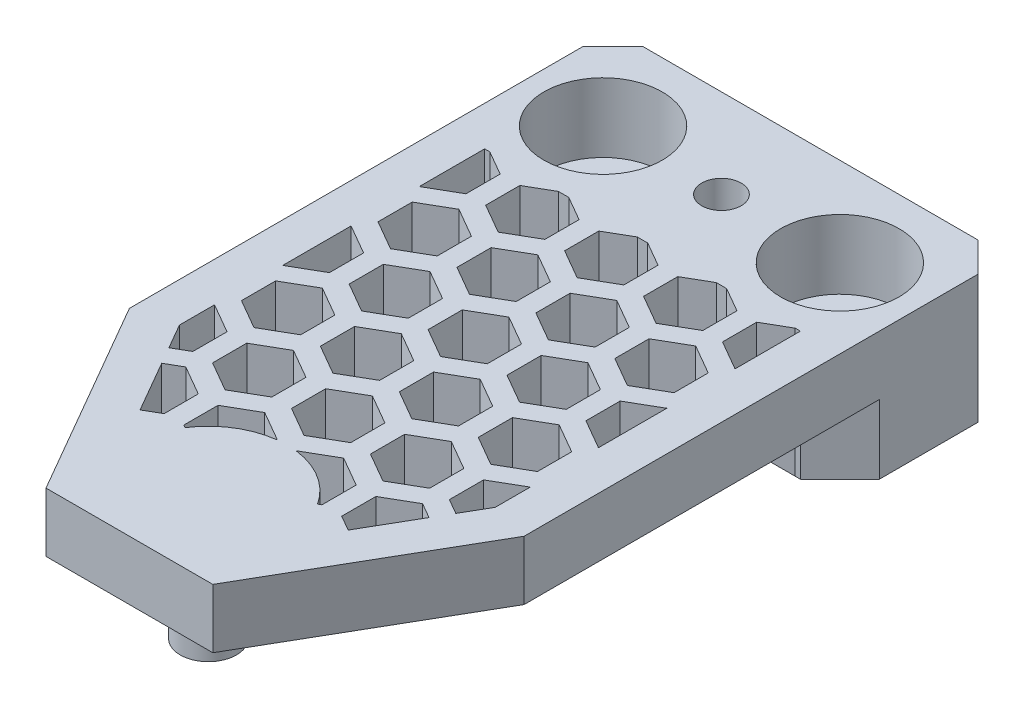
SolidWorks part; units mm, degrees
ref_plane "Front Plane" through (0, 0, 0) normal (0, 0, 1) x (1, 0, 0)
ref_plane "Top Plane" through (0, 0, 0) normal (0, 1, 0) x (1, 0, 0)
ref_plane "Right Plane" through (0, 0, 0) normal (1, 0, 0) x (0, 0, -1)
sketch "Sketch2" plane through (0, 0, 0) normal (0, 1, 0) x (1, 0, 0)
  line L1 (-10, 34) -> (10, 34)
  line L2 (-10, 34) -> (-10, -4)
  line L3 (-10, -4) -> (10, -4)
  line L4 (10, 34) -> (10, -4)
  circle A0 centre (-6, 26) radius 1.5
  circle A1 centre (6, 26) radius 1.5
  circle A2 centre (0, 0) radius 0.5
  circle A3 centre (0, 26) radius 1
  dimension "D1" = 26
  dimension "D2" = 26
  dimension "D3" = 3
  dimension "D4" = 3
  dimension "D5" = 26
  dimension "D6" = 2
  dimension "D7" = 20
  dimension "D8" = 1
  dimension "D9" = 8
extrude "Boss-Extrude1" add sketch "Sketch2" along normal blind 3
chamfer "Chamfer2" distance 10 angle 30 2 edges at (-10, 1.5, 4) (10, 1.5, 4) first distance on face at (-10, 1.5, -15) first distance on face at (10, 1.5, -15)
sketch "Sketch3" plane through (0, 3, 0) normal (0, 1, 0) x (1, 0, 0)
  circle A0 centre (0, 0) radius 1.425
  dimension "D1" = 2.85
extrude "Boss-Extrude2" add sketch "Sketch3" against normal blind 6.5
sketch "Sketch5" plane through (0, 0, 0) normal (0, -1, 0) x (1, 0, 0)
  line L1 (10, -6) -> (10, -34) construction
  line L2 (-10, -34) -> (10, -34)
  line L3 (-10, -34) -> (-10, -22)
  line L4 (-10, -22) -> (10, -22)
  line L5 (10, -34) -> (10, -22)
  circle A0 centre (-6, -26) radius 1.5
  circle A1 centre (6, -26) radius 1.5
  dimension "D1" = 12
extrude "Boss-Extrude3" add sketch "Sketch5" along normal blind 3.5
chamfer "Chamfer3" distance 5 angle 45 2 edges at (10, -0.25, -34) (-10, -0.25, -34)
chamfer "Chamfer4" distance 3.5 angle 45 1 edges at (0, 3, -34)
sketch "Sketch12" plane through (10, 0, 0) normal (1, 0, 0) x (0, 0, -1)
  line L0 (22, 0) -> (18.5, 0)
  line L1 (6, 0) -> (22, 0) construction
  line L2 (22, 0) -> (22, -3.5)
  line L3 (22, -3.5) -> (18.5, 0)
  dimension "D1" = 3.5
extrude "Boss-Extrude6" add sketch "Sketch12" against normal up to surface (20 mm away) up to face at (-10, -0.1667, -19)
sketch "Sketch13" plane through (0, -3.5, 0) normal (0, -1, 0) x (1, 0, 0)
  line L0 (-10, -24) -> (-4.5, -18.5)
  line L2 (-10, -22) -> (-10, -29) construction
  line L4 (-10, -18.5) -> (10, -18.5) construction
  line L5 (-4.5, -18.5) -> (-10, -18.5)
  line L6 (-10, -18.5) -> (-10, -24)
  line L7 (10, -22) -> (-10, -22) construction
  line L8 (4.5, -18.5) -> (10, -24)
  line L9 (10, -29) -> (10, -22) construction
  line L10 (10, -24) -> (10, -18.5)
  line L11 (10, -18.5) -> (4.5, -18.5)
  line L12 (-8, -22) -> (-8, -18.5)
  line L13 (8, -22) -> (8, -18.5)
  line M8 (10, -29) -> (10, -22)
  line M9 (10, -22) -> (-10, -22)
  line M10 (-10, -22) -> (-10, -29)
  dimension "D1" = 2
  dimension "D2" = 45
  dimension "D3" = 2
  dimension "D4" = 45
extrude "Cut-Extrude14" cut sketch "Sketch13" against normal up to surface (3.5 mm away) contours L12 L5 L6 M9 | L0 M10 M9 | L13 L10 L11 M9 | L8 M9 M8 region at (-9.3333, -3.5, -22.6667) region at (9, -3.5, -20.25) region at (9.3333, -3.5, -22.6667) region at (-9, -3.5, -20.25) up to face at (0, 0, 1.425)
sketch "Sketch6" plane through (0, 0, 0) normal (0, -1, 0) x (1, 0, 0)
  line L0 (-10, -23) -> (10, -23)
  line L1 (-10, -24) -> (-10, -6) construction
  line L2 (10, -6) -> (10, -24) construction
  line L3 (0, -4) -> (0, -23)
  line L4 (4, -11.7679) -> (2.5, -12.634)
  line L5 (0, -15.2321) -> (1.5, -14.366)
  line L6 (1.5, -14.366) -> (1.5, -12.634)
  line L7 (1.5, -12.634) -> (0, -11.7679)
  line L8 (0, -11.7679) -> (-1.5, -12.634)
  line L9 (-1.5, -12.634) -> (-1.5, -14.366)
  line L10 (-1.5, -14.366) -> (0, -15.2321)
  line L11 (5.5, -12.634) -> (4, -11.7679)
  line L12 (5.5, -14.366) -> (5.5, -12.634)
  line L13 (4, -15.2321) -> (5.5, -14.366)
  line L14 (2.5, -14.366) -> (4, -15.2321)
  line L15 (2.5, -12.634) -> (2.5, -14.366)
  line L16 (8, -11.7679) -> (6.5, -12.634)
  line L17 (9.5, -12.634) -> (8, -11.7679)
  line L18 (9.5, -14.366) -> (9.5, -12.634)
  line L19 (8, -15.2321) -> (9.5, -14.366)
  line L20 (6.5, -14.366) -> (8, -15.2321)
  line L21 (6.5, -12.634) -> (6.5, -14.366)
  line L22 (-4, -11.7679) -> (-5.5, -12.634)
  line L23 (-2.5, -12.634) -> (-4, -11.7679)
  line L24 (-2.5, -14.366) -> (-2.5, -12.634)
  line L25 (-4, -15.2321) -> (-2.5, -14.366)
  line L26 (-5.5, -14.366) -> (-4, -15.2321)
  line L27 (-5.5, -12.634) -> (-5.5, -14.366)
  line L28 (-8, -11.7679) -> (-9.5, -12.634)
  line L29 (-6.5, -12.634) -> (-8, -11.7679)
  line L30 (-6.5, -14.366) -> (-6.5, -12.634)
  line L31 (-8, -15.2321) -> (-6.5, -14.366)
  line L32 (-9.5, -14.366) -> (-8, -15.2321)
  line L33 (-9.5, -12.634) -> (-9.5, -14.366)
  line L34 (2, -15.2321) -> (0.5, -16.0981)
  line L35 (-2, -18.6962) -> (-0.5, -17.8301)
  line L36 (-0.5, -17.8301) -> (-0.5, -16.0981)
  line L37 (-0.5, -16.0981) -> (-2, -15.2321)
  line L38 (-2, -15.2321) -> (-3.5, -16.0981)
  line L39 (-3.5, -16.0981) -> (-3.5, -17.8301)
  line L40 (-3.5, -17.8301) -> (-2, -18.6962)
  line L41 (3.5, -16.0981) -> (2, -15.2321)
  line L42 (3.5, -17.8301) -> (3.5, -16.0981)
  line L43 (2, -18.6962) -> (3.5, -17.8301)
  line L44 (0.5, -17.8301) -> (2, -18.6962)
  line L45 (0.5, -16.0981) -> (0.5, -17.8301)
  line L46 (6, -15.2321) -> (4.5, -16.0981)
  line L47 (7.5, -16.0981) -> (6, -15.2321)
  line L48 (7.5, -17.8301) -> (7.5, -16.0981)
  line L49 (6, -18.6962) -> (7.5, -17.8301)
  line L50 (4.5, -17.8301) -> (6, -18.6962)
  line L51 (4.5, -16.0981) -> (4.5, -17.8301)
  line L52 (-2, -15.2321) -> (-3.5, -16.0981)
  line L53 (-0.5, -16.0981) -> (-2, -15.2321)
  line L54 (-0.5, -17.8301) -> (-0.5, -16.0981)
  line L55 (-2, -18.6962) -> (-0.5, -17.8301)
  line L56 (-3.5, -17.8301) -> (-2, -18.6962)
  line L57 (-3.5, -16.0981) -> (-3.5, -17.8301)
  line L58 (2, -8.3121) -> (0.5, -9.1781)
  line L59 (3.5, -9.1781) -> (2, -8.3121)
  line L60 (3.5, -10.9101) -> (3.5, -9.1781)
  line L61 (2, -11.7762) -> (3.5, -10.9101)
  line L62 (0.5, -10.9101) -> (2, -11.7762)
  line L63 (0.5, -9.1781) -> (0.5, -10.9101)
  line L64 (6, -8.3121) -> (4.5, -9.1781)
  line L65 (7.5, -9.1781) -> (6, -8.3121)
  line L66 (7.5, -10.9101) -> (7.5, -9.1781)
  line L67 (6, -11.7762) -> (7.5, -10.9101)
  line L68 (4.5, -10.9101) -> (6, -11.7762)
  line L69 (4.5, -9.1781) -> (4.5, -10.9101)
  line L70 (2, -1.3921) -> (0.5, -2.2581)
  line L71 (3.5, -2.2581) -> (2, -1.3921)
  line L72 (3.5, -3.9901) -> (3.5, -2.2581)
  line L73 (2, -4.8562) -> (3.5, -3.9901)
  line L74 (0.5, -3.9901) -> (2, -4.8562)
  line L75 (0.5, -2.2581) -> (0.5, -3.9901)
  line L76 (6, -1.3921) -> (4.5, -2.2581)
  line L77 (7.5, -2.2581) -> (6, -1.3921)
  line L78 (7.5, -3.9901) -> (7.5, -2.2581)
  line L79 (6, -4.8562) -> (7.5, -3.9901)
  line L80 (4.5, -3.9901) -> (6, -4.8562)
  line L81 (4.5, -2.2581) -> (4.5, -3.9901)
  line L82 (-2, -8.3121) -> (-3.5, -9.1781)
  line L83 (-0.5, -9.1781) -> (-2, -8.3121)
  line L84 (-0.5, -10.9101) -> (-0.5, -9.1781)
  line L85 (-2, -11.7762) -> (-0.5, -10.9101)
  line L86 (-3.5, -10.9101) -> (-2, -11.7762)
  line L87 (-3.5, -9.1781) -> (-3.5, -10.9101)
  line L88 (-2, -1.3921) -> (-3.5, -2.2581)
  line L89 (-0.5, -2.2581) -> (-2, -1.3921)
  line L90 (-0.5, -3.9901) -> (-0.5, -2.2581)
  line L91 (-2, -4.8562) -> (-0.5, -3.9901)
  line L92 (-3.5, -3.9901) -> (-2, -4.8562)
  line L93 (-3.5, -2.2581) -> (-3.5, -3.9901)
  line L94 (-6, -15.2321) -> (-7.5, -16.0981)
  line L95 (-4.5, -16.0981) -> (-6, -15.2321)
  line L96 (-4.5, -17.8301) -> (-4.5, -16.0981)
  line L97 (-6, -18.6962) -> (-4.5, -17.8301)
  line L98 (-7.5, -17.8301) -> (-6, -18.6962)
  line L99 (-7.5, -16.0981) -> (-7.5, -17.8301)
  line L100 (-6, -8.3121) -> (-7.5, -9.1781)
  line L101 (-4.5, -9.1781) -> (-6, -8.3121)
  line L102 (-4.5, -10.9101) -> (-4.5, -9.1781)
  line L103 (-6, -11.7762) -> (-4.5, -10.9101)
  line L104 (-7.5, -10.9101) -> (-6, -11.7762)
  line L105 (-7.5, -9.1781) -> (-7.5, -10.9101)
  line L106 (-6, -1.3921) -> (-7.5, -2.2581)
  line L107 (-4.5, -2.2581) -> (-6, -1.3921)
  line L108 (-4.5, -3.9901) -> (-4.5, -2.2581)
  line L109 (-6, -4.8562) -> (-4.5, -3.9901)
  line L110 (-7.5, -3.9901) -> (-6, -4.8562)
  line L111 (-7.5, -2.2581) -> (-7.5, -3.9901)
  line L112 (-2, -8.3121) -> (-3.5, -9.1781)
  line L113 (-0.5, -9.1781) -> (-2, -8.3121)
  line L114 (-0.5, -10.9101) -> (-0.5, -9.1781)
  line L115 (-2, -11.7762) -> (-0.5, -10.9101)
  line L116 (-3.5, -10.9101) -> (-2, -11.7762)
  line L117 (-3.5, -9.1781) -> (-3.5, -10.9101)
  line L118 (-2, -1.3921) -> (-3.5, -2.2581)
  line L119 (-0.5, -2.2581) -> (-2, -1.3921)
  line L120 (-0.5, -3.9901) -> (-0.5, -2.2581)
  line L121 (-2, -4.8562) -> (-0.5, -3.9901)
  line L122 (-3.5, -3.9901) -> (-2, -4.8562)
  line L123 (-3.5, -2.2581) -> (-3.5, -3.9901)
  line L124 (4, -4.8479) -> (2.5, -5.714)
  line L125 (0, -8.3121) -> (1.5, -7.446)
  line L126 (1.5, -7.446) -> (1.5, -5.714)
  line L127 (1.5, -5.714) -> (0, -4.8479)
  line L128 (0, -4.8479) -> (-1.5, -5.714)
  line L129 (-1.5, -5.714) -> (-1.5, -7.446)
  line L130 (-1.5, -7.446) -> (0, -8.3121)
  line L131 (5.5, -5.714) -> (4, -4.8479)
  line L132 (5.5, -7.446) -> (5.5, -5.714)
  line L133 (4, -8.3121) -> (5.5, -7.446)
  line L134 (2.5, -7.446) -> (4, -8.3121)
  line L135 (2.5, -5.714) -> (2.5, -7.446)
  line L136 (8, -4.8479) -> (6.5, -5.714)
  line L137 (9.5, -5.714) -> (8, -4.8479)
  line L138 (9.5, -7.446) -> (9.5, -5.714)
  line L139 (8, -8.3121) -> (9.5, -7.446)
  line L140 (6.5, -7.446) -> (8, -8.3121)
  line L141 (6.5, -5.714) -> (6.5, -7.446)
  line L142 (-4, -4.8479) -> (-5.5, -5.714)
  line L143 (-2.5, -5.714) -> (-4, -4.8479)
  line L144 (-2.5, -7.446) -> (-2.5, -5.714)
  line L145 (-4, -8.3121) -> (-2.5, -7.446)
  line L146 (-5.5, -7.446) -> (-4, -8.3121)
  line L147 (-5.5, -5.714) -> (-5.5, -7.446)
  line L148 (-8, -4.8479) -> (-9.5, -5.714)
  line L149 (-6.5, -5.714) -> (-8, -4.8479)
  line L150 (-6.5, -7.446) -> (-6.5, -5.714)
  line L151 (-8, -8.3121) -> (-6.5, -7.446)
  line L152 (-9.5, -7.446) -> (-8, -8.3121)
  line L153 (-9.5, -5.714) -> (-9.5, -7.446)
  line L154 (4, -4.8479) -> (2.5, -5.714)
  line L155 (0, -8.3121) -> (1.5, -7.446)
  line L156 (1.5, -7.446) -> (1.5, -5.714)
  line L157 (1.5, -5.714) -> (0, -4.8479)
  line L158 (0, -4.8479) -> (-1.5, -5.714)
  line L159 (-1.5, -5.714) -> (-1.5, -7.446)
  line L160 (-1.5, -7.446) -> (0, -8.3121)
  line L161 (5.5, -5.714) -> (4, -4.8479)
  line L162 (5.5, -7.446) -> (5.5, -5.714)
  line L163 (4, -8.3121) -> (5.5, -7.446)
  line L164 (2.5, -7.446) -> (4, -8.3121)
  line L165 (2.5, -5.714) -> (2.5, -7.446)
  line L166 (8, -4.8479) -> (6.5, -5.714)
  line L167 (9.5, -5.714) -> (8, -4.8479)
  line L168 (9.5, -7.446) -> (9.5, -5.714)
  line L169 (8, -8.3121) -> (9.5, -7.446)
  line L170 (6.5, -7.446) -> (8, -8.3121)
  line L171 (6.5, -5.714) -> (6.5, -7.446)
  line L172 (4, -11.7679) -> (2.5, -12.634)
  line L173 (0, -15.2321) -> (1.5, -14.366)
  line L174 (1.5, -14.366) -> (1.5, -12.634)
  line L175 (1.5, -12.634) -> (0, -11.7679)
  line L176 (0, -11.7679) -> (-1.5, -12.634)
  line L177 (-1.5, -12.634) -> (-1.5, -14.366)
  line L178 (-1.5, -14.366) -> (0, -15.2321)
  line L179 (5.5, -12.634) -> (4, -11.7679)
  line L180 (5.5, -14.366) -> (5.5, -12.634)
  line L181 (4, -15.2321) -> (5.5, -14.366)
  line L182 (2.5, -14.366) -> (4, -15.2321)
  line L183 (2.5, -12.634) -> (2.5, -14.366)
  line L184 (8, -11.7679) -> (6.5, -12.634)
  line L185 (9.5, -12.634) -> (8, -11.7679)
  line L186 (9.5, -14.366) -> (9.5, -12.634)
  line L187 (8, -15.2321) -> (9.5, -14.366)
  line L188 (6.5, -14.366) -> (8, -15.2321)
  line L189 (6.5, -12.634) -> (6.5, -14.366)
  line L190 (-4, -11.7679) -> (-5.5, -12.634)
  line L191 (-2.5, -12.634) -> (-4, -11.7679)
  line L192 (-2.5, -14.366) -> (-2.5, -12.634)
  line L193 (-4, -15.2321) -> (-2.5, -14.366)
  line L194 (-5.5, -14.366) -> (-4, -15.2321)
  line L195 (-5.5, -12.634) -> (-5.5, -14.366)
  line L196 (-8, -11.7679) -> (-9.5, -12.634)
  line L197 (-6.5, -12.634) -> (-8, -11.7679)
  line L198 (-6.5, -14.366) -> (-6.5, -12.634)
  line L199 (-8, -15.2321) -> (-6.5, -14.366)
  line L200 (-9.5, -14.366) -> (-8, -15.2321)
  line L201 (-9.5, -12.634) -> (-9.5, -14.366)
  line L202 (-4, -4.8479) -> (-5.5, -5.714)
  line L203 (-2.5, -5.714) -> (-4, -4.8479)
  line L204 (-2.5, -7.446) -> (-2.5, -5.714)
  line L205 (-4, -8.3121) -> (-2.5, -7.446)
  line L206 (-5.5, -7.446) -> (-4, -8.3121)
  line L207 (-5.5, -5.714) -> (-5.5, -7.446)
  line L208 (-8, -4.8479) -> (-9.5, -5.714)
  line L209 (-6.5, -5.714) -> (-8, -4.8479)
  line L210 (-6.5, -7.446) -> (-6.5, -5.714)
  line L211 (-8, -8.3121) -> (-6.5, -7.446)
  line L212 (-9.5, -7.446) -> (-8, -8.3121)
  line L213 (-9.5, -5.714) -> (-9.5, -7.446)
  line L214 (4, -18.6879) -> (2.5, -19.554)
  line L215 (0, -22.1521) -> (1.5, -21.286)
  line L216 (1.5, -21.286) -> (1.5, -19.554)
  line L217 (1.5, -19.554) -> (0, -18.6879)
  line L218 (0, -18.6879) -> (-1.5, -19.554)
  line L219 (-1.5, -19.554) -> (-1.5, -21.286)
  line L220 (-1.5, -21.286) -> (0, -22.1521)
  line L221 (5.5, -19.554) -> (4, -18.6879)
  line L222 (5.5, -21.286) -> (5.5, -19.554)
  line L223 (4, -22.1521) -> (5.5, -21.286)
  line L224 (2.5, -21.286) -> (4, -22.1521)
  line L225 (2.5, -19.554) -> (2.5, -21.286)
  line L226 (8, -18.6879) -> (6.5, -19.554)
  line L227 (9.5, -19.554) -> (8, -18.6879)
  line L228 (9.5, -21.286) -> (9.5, -19.554)
  line L229 (8, -22.1521) -> (9.5, -21.286)
  line L230 (6.5, -21.286) -> (8, -22.1521)
  line L231 (6.5, -19.554) -> (6.5, -21.286)
  line L232 (8, -23) -> (8, -6.5359)
  line L233 (3.9765, 0.433) -> (8, -6.5359)
  line L234 (10, -6) -> (4.2265, 4) construction
  line L235 (-8, -23) -> (-8, -6.5359)
  line L236 (-3.9765, 0.433) -> (-8, -6.5359)
  line L237 (-4, -18.6879) -> (-5.5, -19.554)
  line L238 (-2.5, -19.554) -> (-4, -18.6879)
  line L239 (-2.5, -21.286) -> (-2.5, -19.554)
  line L240 (-4, -22.1521) -> (-2.5, -21.286)
  line L241 (4, -18.6879) -> (2.5, -19.554) [skipped]
  line L242 (0, -22.1521) -> (1.5, -21.286) [skipped]
  line L243 (1.5, -21.286) -> (1.5, -19.554) [skipped]
  line L244 (1.5, -19.554) -> (0, -18.6879) [skipped]
  line L245 (0, -18.6879) -> (-1.5, -19.554) [skipped]
  line L246 (-1.5, -19.554) -> (-1.5, -21.286) [skipped]
  line L247 (-1.5, -21.286) -> (0, -22.1521) [skipped]
  line L248 (5.5, -19.554) -> (4, -18.6879) [skipped]
  line L249 (5.5, -21.286) -> (5.5, -19.554) [skipped]
  line L250 (4, -22.1521) -> (5.5, -21.286) [skipped]
  line L251 (2.5, -21.286) -> (4, -22.1521) [skipped]
  line L252 (2.5, -19.554) -> (2.5, -21.286) [skipped]
  line L253 (8, -18.6879) -> (6.5, -19.554) [skipped]
  line L254 (9.5, -19.554) -> (8, -18.6879) [skipped]
  line L255 (9.5, -21.286) -> (9.5, -19.554) [skipped]
  line L256 (8, -22.1521) -> (9.5, -21.286) [skipped]
  line L257 (6.5, -21.286) -> (8, -22.1521) [skipped]
  line L258 (6.5, -19.554) -> (6.5, -21.286) [skipped]
  line L259 (-4, -18.6879) -> (-5.5, -19.554) [skipped]
  line L260 (-2.5, -19.554) -> (-4, -18.6879) [skipped]
  line L261 (-2.5, -21.286) -> (-2.5, -19.554) [skipped]
  line L262 (-4, -22.1521) -> (-2.5, -21.286) [skipped]
  line L263 (-5.5, -21.286) -> (-4, -22.1521) [skipped]
  line L264 (-5.5, -19.554) -> (-5.5, -21.286) [skipped]
  line L265 (-8, -18.6879) -> (-9.5, -19.554) [skipped]
  line L266 (-6.5, -19.554) -> (-8, -18.6879) [skipped]
  line L267 (-6.5, -21.286) -> (-6.5, -19.554) [skipped]
  line L268 (-8, -22.1521) -> (-6.5, -21.286) [skipped]
  line L269 (-9.5, -21.286) -> (-8, -22.1521) [skipped]
  line L270 (-9.5, -19.554) -> (-9.5, -21.286) [skipped]
  line L271 (-5.5, -21.286) -> (-4, -22.1521)
  line L272 (-5.5, -19.554) -> (-5.5, -21.286)
  line L273 (-8, -18.6879) -> (-9.5, -19.554)
  line L274 (-6.5, -19.554) -> (-8, -18.6879)
  line L275 (-6.5, -21.286) -> (-6.5, -19.554)
  line L276 (-8, -22.1521) -> (-6.5, -21.286)
  line L277 (-9.5, -21.286) -> (-8, -22.1521)
  line L278 (-9.5, -19.554) -> (-9.5, -21.286)
  line L279 (4, -18.6879) -> (2.5, -19.554)
  line L280 (0, -22.1521) -> (1.5, -21.286)
  line L281 (1.5, -21.286) -> (1.5, -19.554)
  line L282 (1.5, -19.554) -> (0, -18.6879)
  line L283 (0, -18.6879) -> (-1.5, -19.554)
  line L284 (-1.5, -19.554) -> (-1.5, -21.286)
  line L285 (-1.5, -21.286) -> (0, -22.1521)
  line L286 (5.5, -19.554) -> (4, -18.6879)
  line L287 (5.5, -21.286) -> (5.5, -19.554)
  line L288 (4, -22.1521) -> (5.5, -21.286)
  line L289 (2.5, -21.286) -> (4, -22.1521)
  line L290 (2.5, -19.554) -> (2.5, -21.286)
  line L291 (8, -18.6879) -> (6.5, -19.554)
  line L292 (9.5, -19.554) -> (8, -18.6879)
  line L293 (9.5, -21.286) -> (9.5, -19.554)
  line L294 (8, -22.1521) -> (9.5, -21.286)
  line L295 (6.5, -21.286) -> (8, -22.1521)
  line L296 (6.5, -19.554) -> (6.5, -21.286)
  line L297 (-4, -18.6879) -> (-5.5, -19.554)
  line L298 (-2.5, -19.554) -> (-4, -18.6879)
  line L299 (-2.5, -21.286) -> (-2.5, -19.554)
  line L300 (-4, -22.1521) -> (-2.5, -21.286)
  line L301 (-5.5, -21.286) -> (-4, -22.1521)
  line L302 (-5.5, -19.554) -> (-5.5, -21.286)
  line L303 (4, -4.8479) -> (2.5, -5.714) [skipped]
  line L304 (0, -8.3121) -> (1.5, -7.446) [skipped]
  line L305 (1.5, -7.446) -> (1.5, -5.714) [skipped]
  line L306 (1.5, -5.714) -> (0, -4.8479) [skipped]
  line L307 (0, -4.8479) -> (-1.5, -5.714) [skipped]
  line L308 (-1.5, -5.714) -> (-1.5, -7.446) [skipped]
  line L309 (-1.5, -7.446) -> (0, -8.3121) [skipped]
  line L310 (5.5, -5.714) -> (4, -4.8479) [skipped]
  line L311 (5.5, -7.446) -> (5.5, -5.714) [skipped]
  line L312 (4, -8.3121) -> (5.5, -7.446) [skipped]
  line L313 (2.5, -7.446) -> (4, -8.3121) [skipped]
  line L314 (2.5, -5.714) -> (2.5, -7.446) [skipped]
  line L315 (8, -4.8479) -> (6.5, -5.714) [skipped]
  line L316 (9.5, -5.714) -> (8, -4.8479) [skipped]
  line L317 (9.5, -7.446) -> (9.5, -5.714) [skipped]
  line L318 (8, -8.3121) -> (9.5, -7.446) [skipped]
  line L319 (6.5, -7.446) -> (8, -8.3121) [skipped]
  line L320 (6.5, -5.714) -> (6.5, -7.446) [skipped]
  line L321 (-4, -4.8479) -> (-5.5, -5.714) [skipped]
  line L322 (-2.5, -5.714) -> (-4, -4.8479) [skipped]
  line L323 (-2.5, -7.446) -> (-2.5, -5.714) [skipped]
  line L324 (-4, -8.3121) -> (-2.5, -7.446) [skipped]
  line L325 (-5.5, -7.446) -> (-4, -8.3121) [skipped]
  line L326 (-5.5, -5.714) -> (-5.5, -7.446) [skipped]
  line L327 (-8, -4.8479) -> (-9.5, -5.714) [skipped]
  line L328 (-6.5, -5.714) -> (-8, -4.8479) [skipped]
  line L329 (-6.5, -7.446) -> (-6.5, -5.714) [skipped]
  line L330 (-8, -8.3121) -> (-6.5, -7.446) [skipped]
  line L331 (-9.5, -7.446) -> (-8, -8.3121) [skipped]
  line L332 (-9.5, -5.714) -> (-9.5, -7.446) [skipped]
  line L333 (-8, -18.6879) -> (-9.5, -19.554)
  line L334 (-6.5, -19.554) -> (-8, -18.6879)
  line L335 (-6.5, -21.286) -> (-6.5, -19.554)
  line L336 (-8, -22.1521) -> (-6.5, -21.286)
  line L337 (-9.5, -21.286) -> (-8, -22.1521)
  line L338 (-9.5, -19.554) -> (-9.5, -21.286)
  line L339 (-9.5, -22) -> (11.458, -22)
  line L369 (-6, -15.2321) -> (-7.5, -16.0981) [skipped]
  line L370 (-4.5, -16.0981) -> (-6, -15.2321) [skipped]
  line L371 (-4.5, -17.8301) -> (-4.5, -16.0981) [skipped]
  line L372 (-6, -18.6962) -> (-4.5, -17.8301) [skipped]
  line L373 (-7.5, -17.8301) -> (-6, -18.6962) [skipped]
  line L374 (-7.5, -16.0981) -> (-7.5, -17.8301) [skipped]
  line L375 (2, -15.2321) -> (0.5, -16.0981) [skipped]
  line L376 (0.5, -16.0981) -> (0.5, -17.8301) [skipped]
  line L377 (2, -15.2321) -> (0.5, -16.0981) [skipped]
  line L378 (3.5, -17.8301) -> (3.5, -16.0981) [skipped]
  line L379 (2, -18.6962) -> (3.5, -17.8301) [skipped]
  line L380 (0.5, -17.8301) -> (2, -18.6962) [skipped]
  line L381 (7.5, -17.8301) -> (7.5, -16.0981) [skipped]
  line L382 (6, -18.6962) -> (7.5, -17.8301) [skipped]
  line L383 (4.5, -17.8301) -> (6, -18.6962) [skipped]
  line L384 (4.5, -16.0981) -> (4.5, -17.8301) [skipped]
  line L385 (3.5, -17.8301) -> (3.5, -16.0981) [skipped]
  line L386 (2, -18.6962) -> (3.5, -17.8301) [skipped]
  line L387 (0.5, -17.8301) -> (2, -18.6962) [skipped]
  line L388 (0.5, -16.0981) -> (0.5, -17.8301) [skipped]
  line L389 (3.5, -16.0981) -> (2, -15.2321) [skipped]
  line L390 (6, -15.2321) -> (4.5, -16.0981) [skipped]
  line L391 (7.5, -16.0981) -> (6, -15.2321) [skipped]
  line L392 (3.5, -16.0981) -> (2, -15.2321) [skipped]
  circle A0 centre (0, 0) radius 4
  circle A1 centre (0, -13.5) radius 1.5 construction
  circle A2 centre (-2, -16.9641) radius 1.5 construction
  line M444 (-8, -18.5) -> (8, -18.5)
  line M446 (8, -22) -> (10, -24)
  line M447 (-8, -22) -> (-8, -18.5)
  dimension "D1" = 3
  dimension "D5" = 60
  dimension "D6" = 60
  dimension "D12" = 2
  dimension "D13" = 2
  dimension "D2" = 3
  dimension "D3" = 3
  dimension "D7" = 3
  dimension "D8" = 2
  dimension "D10" = 2
  dimension "D11" = 2
extrude "Cut-Extrude12" cut sketch "Sketch6" against normal blind 3.5 and the other way blind 3.5 contours L216 L217 L3 L215 | L219 L220 L3 L218 | L214 L225 L224 L223 L222 L221 | L46 L51 L50 L49 L48 L47 M444 | L34 L45 L44 L43 L42 L41 M444 | L44 L43 M444 | L39 L40 L35 L36 L37 L38 M444 | L40 L35 M444 | L94 L99 L98 L97 L96 L95 M444 | L20 L232 L16 L21 | L4 L15 L14 L13 L12 L11 | L6 L7 L3 L5 | L22 L27 L26 L25 L24 L23 | L235 L31 L30 L29 | L100 L105 L104 L103 L102 L101 | L82 L87 L86 L85 L84 L83 | L58 L63 L62 L61 L60 L59 | L64 L69 L68 L67 L66 L65 | L9 L10 L3 L8 | L149 L236 L235 L151 L150 | L142 L147 L146 L145 L144 L143 | L129 L130 L3 L128 | L126 L127 L3 L125 | L124 L135 L134 L133 L132 L131 | L233 L166 L141 L140 L232 | L233 L76 L81 L80 L79 | A0 L75 L74 L73 L72 L71 | A0 L118 L93 L92 L91 L90 | L107 L236 L110 L109 L108 | L232 L226 L231 M446 | L235 L276 L275 L274 M447 | L237 L272 L271 L240 L239 L238 | L98 L97 M444 | L50 L49 M444 region at (-7.3303, 0, -20.4116) region at (-0.6697, 0, -20.4116) region at (0.6697, 0, -20.4116) region at (-4, 0, -20.4116) region at (7.3303, 0, -20.4116) region at (4, 0, -20.4116) region at (-7.3333, 0, -13.5) region at (-6, 0, -18.5654) region at (-6, 0, -16.9503) region at (-0.6667, 0, -13.5) region at (0.6667, 0, -13.5) region at (-2, 0, -16.9503) region at (-2, 0, -18.5654) region at (2, 0, -18.5654) region at (2, 0, -16.9503) region at (7.3333, 0, -13.5) region at (6, 0, -16.9503) region at (6, 0, -18.5654) region at (-7.2538, 0, -6.7735) region at (-0.6667, 0, -6.58) region at (0.6667, 0, -6.58) region at (7.2538, 0, -6.7735) region at (-5.4284, 0, -3.4541) region at (-2.4168, 0, -3.7597) region at (2.4168, 0, -3.7597) region at (5.4284, 0, -3.4541) region at (4, 0, -13.5) region at (-4, 0, -13.5) region at (2, 0, -10.0441) region at (6, 0, -10.0441) region at (-2, 0, -10.0441) region at (-6, 0, -10.0441) region at (4, 0, -6.58) region at (-4, 0, -6.58)
sketch "Sketch7" plane through (0, 3, 0) normal (0, 1, 0) x (1, 0, 0)
  circle A0 centre (-6, 26) radius 3
  circle A1 centre (6, 26) radius 3
  dimension "D1" = 6
  dimension "D2" = 6
extrude "Cut-Extrude13" cut sketch "Sketch7" against normal blind 3.5
sketch "Sketch9" plane through (0, 0, 0) normal (0, -1, 0) x (1, 0, 0)
  circle A0 centre (0, 0) radius 2.625
  dimension "D1" = 5.25
extrude "Boss-Extrude4" add sketch "Sketch9" along normal blind 0.5
sketch "Sketch10" plane through (0, -3.5, 0) normal (0, -1, 0) x (1, 0, 0)
  circle A0 centre (-6, -26) radius 2.4
  circle A1 centre (6, -26) radius 2.4
  circle A2 centre (-6, -26) radius 1.5
  circle A3 centre (6, -26) radius 1.5
  dimension "D1" = 4.8
  dimension "D2" = 4.8
extrude "Boss-Extrude5" add sketch "Sketch10" along normal blind 0.55
